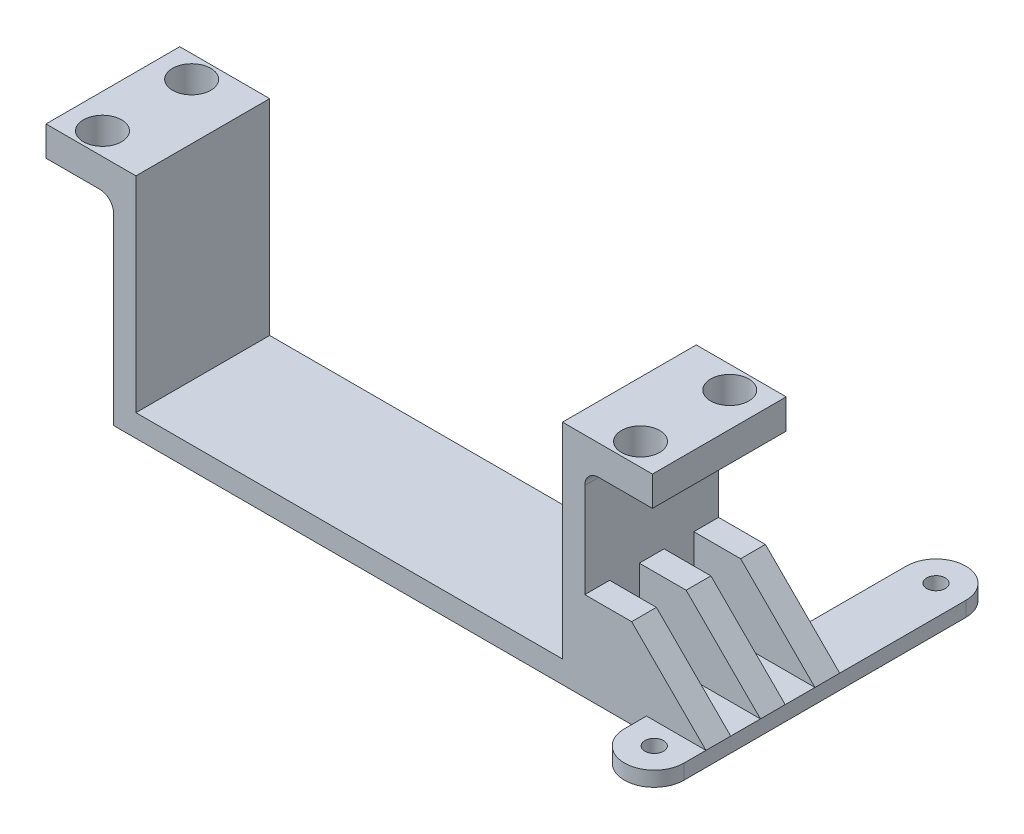
SolidWorks part; units mm, degrees
ref_plane "Front Plane" through (0, 0, 0) normal (0, 0, 1) x (1, 0, 0)
ref_plane "Top Plane" through (0, 0, 0) normal (0, 1, 0) x (1, 0, 0)
ref_plane "Right Plane" through (0, 0, 0) normal (1, 0, 0) x (0, 0, -1)
sketch "Sketch1" plane through (0, 0, 0) normal (0, 0, 1) x (1, 0, 0)
  line L0 (-3.81, 35.052) -> (0, 35.052)
  line L1 (0, 0) -> (72.898, 0)
  line L2 (0, 0) -> (0, 35.052)
  line L4 (72.898, 0) -> (72.898, 35.052)
  line L6 (-3.81, 35.052) -> (-3.81, -3.81)
  line L7 (-3.81, -3.81) -> (76.708, -3.81)
  line L8 (76.708, 35.052) -> (76.708, -3.81)
  line L9 (72.898, 35.052) -> (76.708, 35.052)
  dimension "D1" = 3.81
  dimension "D2" = 3.81
  dimension "D3" = 3.81
  dimension "D4" = 38.862
  dimension "D5" = 72.898
extrude "Boss-Extrude1" add sketch "Sketch1" along normal blind 22.86
sketch "Sketch2" plane through (0, -3.81, 0) normal (0, -1, 0) x (1, 0, 0)
  line L0 (92.329, 26.6192) -> (92.329, -21.5392) construction
  line L2 (87.249, 26.6192) -> (87.249, 22.86)
  line L3 (97.409, 26.6192) -> (97.409, -21.5392)
  line L4 (-3.81, 22.86) -> (76.708, 22.86) construction
  line L5 (76.708, 22.86) -> (76.708, 0) construction
  line L6 (76.708, 22.86) -> (87.249, 22.86)
  line L7 (76.708, 22.86) -> (76.708, 0)
  line L8 (76.708, 0) -> (87.249, 0)
  line L9 (87.249, 0) -> (87.249, -21.5392)
  circle A0 centre (92.329, 26.6192) radius 1.5875
  circle A1 centre (92.329, -21.5392) radius 1.5875
  arc A2 (97.409, 26.6192) -> (87.249, 26.6192) centre (92.329, 26.6192) ccw
  arc A3 (87.249, -21.5392) -> (97.409, -21.5392) centre (92.329, -21.5392) ccw
  point P4 (92.329, 2.54)
  point P5 (76.708, 11.43)
  point P6 (36.449, 22.86)
  point P9 (92.329, 25.0317)
  point P14 (92.329, -19.9517)
  dimension "D2" = 3.175
  dimension "D3" = 5.08
  dimension "D1" = 44.9834
  dimension "D4" = 55.88
  dimension "D5" = 8.89
extrude "Boss-Extrude2" add sketch "Sketch2" against normal blind 2.54
sketch "Sketch4" plane through (0, 35.052, 0) normal (0, 1, 0) x (1, 0, 0)
  line L0 (0, -22.86) -> (-3.81, -22.86) construction
  line L1 (0, 0) -> (-15.367, 0)
  line L2 (0, 0) -> (0, -22.86)
  line L3 (0, -22.86) -> (-15.367, -22.86)
  line L4 (-15.367, 0) -> (-15.367, -22.86)
  line L5 (-3.81, -22.86) -> (-3.81, 0) construction
  line L6 (-9.525, -3.81) -> (-9.525, -19.05) construction
  circle A0 centre (-9.525, -3.81) radius 3.2639
  circle A1 centre (-9.525, -19.05) radius 3.2639
  point P13 (-15.367, -11.43)
  point P14 (-9.525, -11.43)
  dimension "D1" = 6.5278
  dimension "D2" = 5.715
  dimension "D3" = 7.62
  dimension "D4" = 5.842
extrude "Boss-Extrude3" add sketch "Sketch4" against normal blind 5.08
ref_plane "Plane1" through (36.449, 0, 0) normal (1, 0, 0) x (0, 0, -1)
mirror "Mirror1" about plane through (36.449, 0, 0) normal (1, 0, 0) of "Boss-Extrude3"
sketch "Sketch5" plane through (0, -1.27, 0) normal (0, 1, 0) x (1, 0, 0)
  line L0 (97.409, 21.5392) -> (97.409, -26.6192) construction
  line L1 (76.708, 0) -> (97.409, 0)
  line L2 (76.708, 0) -> (76.708, -4.2333)
  line L3 (76.708, -4.2333) -> (97.409, -4.2333)
  line L4 (97.409, 0) -> (97.409, -4.2333)
  line L5 (76.708, -22.86) -> (76.708, 0) construction
  line L6 (76.708, -22.86) -> (97.409, -22.86)
  line L7 (76.708, -22.86) -> (76.708, -18.6267)
  line L8 (76.708, -18.6267) -> (97.409, -18.6267)
  line L9 (97.409, -22.86) -> (97.409, -18.6267)
  line L10 (76.708, -9.3133) -> (97.409, -9.3133)
  line L11 (76.708, -9.3133) -> (76.708, -13.5467)
  line L12 (76.708, -13.5467) -> (97.409, -13.5467)
  line L13 (97.409, -9.3133) -> (97.409, -13.5467)
  dimension "D1" = 5.08
  dimension "D2" = 5.08
extrude "Boss-Extrude4" add sketch "Sketch5" along normal blind 12.7
chamfer "Chamfer1" distance 12.7 angle 45 3 edges at (97.409, 11.43, 20.7433) (97.409, 11.43, 11.43) (97.409, 11.43, 2.1167)
fillet "Fillet1" radius 2.38 2 edges at (76.708, 29.972, 11.43) (-3.81, 29.972, 11.43)
